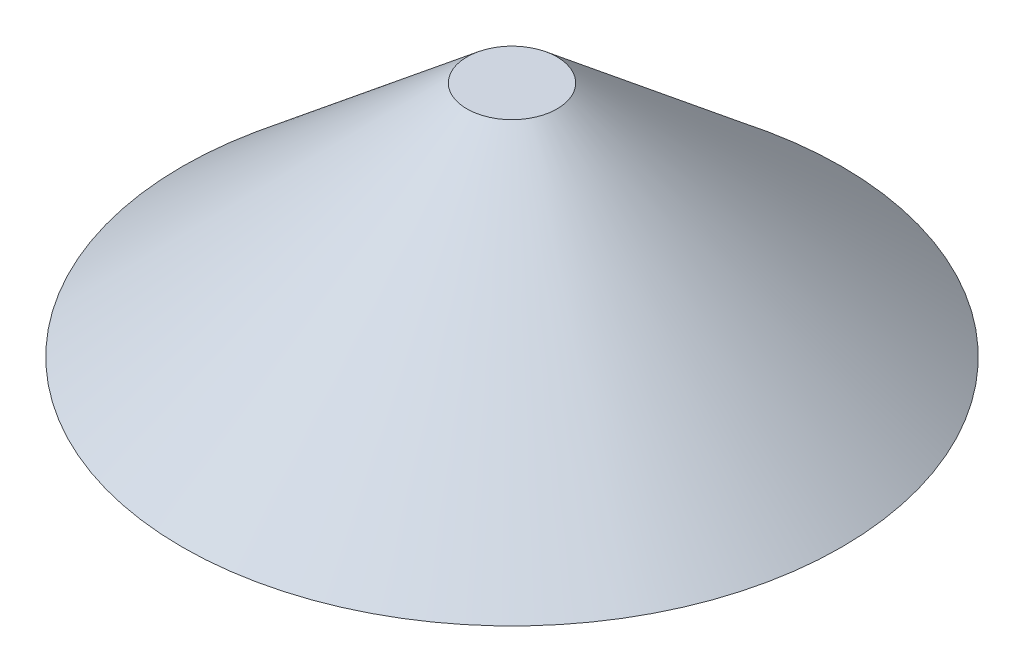
SolidWorks part; units mm, degrees
ref_plane "Front Plane" through (0, 0, 0) normal (0, 0, 1) x (1, 0, 0)
ref_plane "Top Plane" through (0, 0, 0) normal (0, 1, 0) x (1, 0, 0)
ref_plane "Right Plane" through (0, 0, 0) normal (1, 0, 0) x (0, 0, -1)
sketch "Sketch1" plane through (0, 0, 0) normal (0, 0, 1) x (1, 0, 0)
  line L0 (0, 0) -> (-69.5, 0)
  line L1 (-69.5, 0) -> (-9.5, 50)
  line L2 (-9.5, 50) -> (0, 50)
  line L3 (0, 50) -> (0, 0)
  dimension "D1" = 69.5
  dimension "D2" = 60
  dimension "D3" = 50
revolve "Revolve1" add sketch "Sketch1" angle 360 about L3
ref_axis "Axis1" through (0, 50, 0) along (0, -1, 0)
